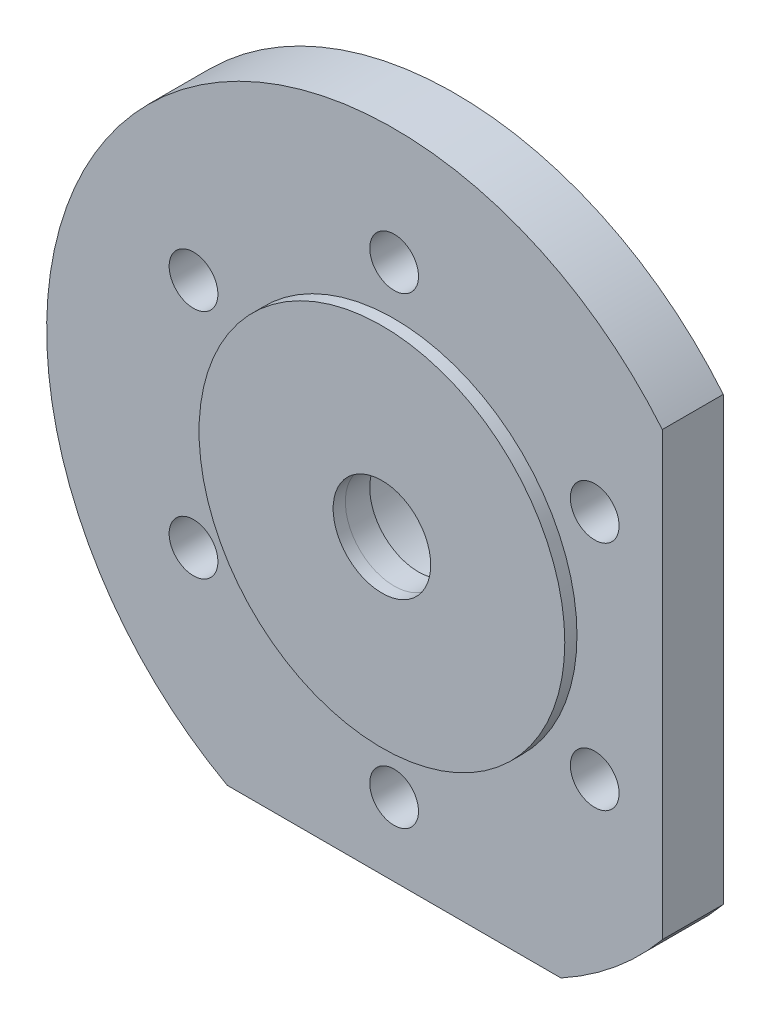
SolidWorks part; units mm, degrees
material "Alumina"
ref_plane "Front Plane" through (0, 0, 0) normal (0, 0, 1) x (1, 0, 0)
ref_plane "Top Plane" through (0, 0, 0) normal (0, 1, 0) x (1, 0, 0)
ref_plane "Right Plane" through (0, 0, 0) normal (1, 0, 0) x (0, 0, -1)
sketch "Sketch1" plane through (0, 0, 0) normal (0, 0, 1) x (1, 0, 0)
  line L0 (0, 0) -> (50000, 0) construction
  line L1 (0, 0) -> (0, 50000) construction
  line L2 (22, 18.1177) -> (22, -18.1177)
  line L3 (13.6839, -25) -> (-13.6839, -25)
  arc A0 (22, 18.1177) -> (-13.6839, -25) centre (0, 0) ccw
  circle A1 centre (0, 0) radius 15
  circle A2 centre (0, 0) radius 19 construction
  arc A3 (13.6839, -25) -> (22, -18.1177) centre (0, 0) ccw
  circle A4 centre (0, 19) radius 2
  circle A5 centre (16.4545, 9.5) radius 2
  circle A6 centre (16.4545, -9.5) radius 2
  circle A7 centre (0, -19) radius 2
  circle A8 centre (-16.4545, -9.5) radius 2
  circle A9 centre (-16.4545, 9.5) radius 2
  circle A10 centre (0, 0) radius 6
  circle A11 centre (0, 0) radius 4
  point P28 (0, 0)
  dimension "D1" = 57
  dimension "D2" = 38
  dimension "D3" = 30
  dimension "D6" = 4
  dimension "D8" = 12
  dimension "D4" = 22
  dimension "D5" = 25
  dimension "D7" = 6
extrude "Boss-Extrude1" add sketch "Sketch1" along normal blind 1 contours A1 A10 | A10 A11 region at (-14.5757, 0, 0) region at (-5.8303, 0, 0)
extrude "Boss-Extrude2" add sketch "Sketch1<4>" against normal blind 5 separate body contours L3 A3 L2 A0 A9 A8 A7 A6 A5 A4 A1 region at (21.2643, 0, 0)
sketch "Sketch1<4>" plane through (0, 0, 0) normal (0, 0, 1) x (1, 0, 0) same geometry as "Sketch1"
extrude "Boss-Extrude3" add sketch "Sketch1<6>" against normal blind 12 contours A1 A10 region at (-14.5757, 0, 0)
sketch "Sketch1<6>" plane through (0, 0, 0) normal (0, 0, 1) x (1, 0, 0) same geometry as "Sketch1"
cosmetic thread "Cosmetic Thread1" parameters "D2"=14
extrude "Boss-Extrude4" add sketch "Sketch1<7>" against normal blind 2 contours A10 A11 region at (-5.8303, 0, 0)
sketch "Sketch1<7>" plane through (0, 0, 0) normal (0, 0, 1) x (1, 0, 0) same geometry as "Sketch1"
